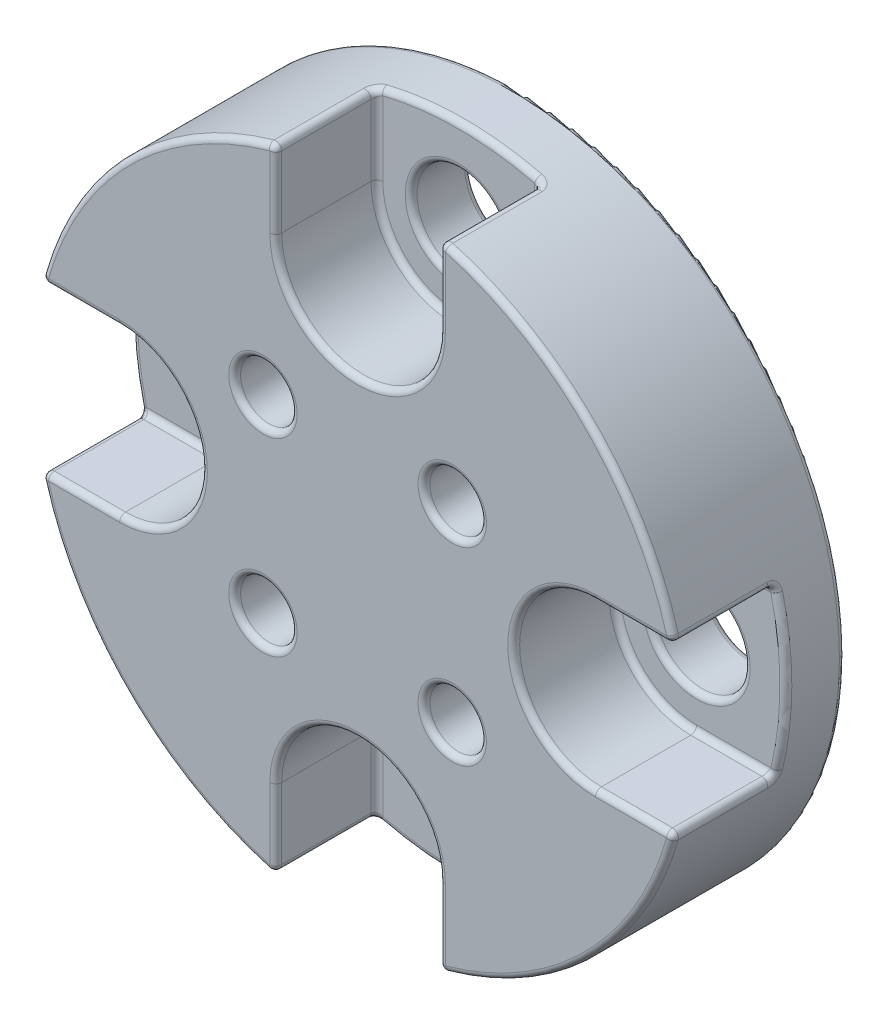
SolidWorks part; units mm, degrees
ref_plane "정면" through (0, 0, 0) normal (0, 0, 1) x (1, 0, 0)
ref_plane "윗면" through (0, 0, 0) normal (0, 1, 0) x (1, 0, 0)
ref_plane "우측면" through (0, 0, 0) normal (1, 0, 0) x (0, 0, -1)
sketch "스케치1" plane through (0, 0, 0) normal (0, 0, 1) x (1, 0, 0)
  circle A0 centre (0, 0) radius 15
  circle A1 centre (0, 0) radius 11.5
  dimension "D1" = 23
  dimension "D2" = 30
extrude "보스-돌출1" add sketch "스케치1" against normal blind 1.8 contours A0 A1 region at (-14.5757, 0, 0)
extrude "보스-돌출2" add sketch "스케치1<3>" along normal blind 2 contours A0 A1 | A1 region at (-14.5757, 0, 0)
sketch "스케치1<3>" plane through (0, 0, 0) normal (0, 0, 1) x (1, 0, 0) same geometry as "스케치1"
sketch "스케치2" plane through (0, 0, 2) normal (0, 0, 1) x (1, 0, 0)
  circle A0 centre (0, 8) radius 1.6
  circle A1 centre (8, 0) radius 1.6
  circle A2 centre (0, -8) radius 1.6
  circle A3 centre (-8, 0) radius 1.6
  point P12 (0, 0)
  dimension "D1" = 3.2
  dimension "D2" = 8
  dimension "D3" = 4
extrude "컷-돌출1" cut sketch "스케치2" against normal blind 2
sketch "스케치3" plane through (0, 0, 2) normal (0, 0, 1) x (1, 0, 0)
  line L0 (-8, 2.75) -> (-14.7458, 2.75)
  line L1 (-8, -2.75) -> (-14.7458, -2.75)
  line L2 (8, 2.75) -> (14.7458, 2.75)
  line L3 (8, -2.75) -> (14.7458, -2.75)
  line L4 (2.75, 8) -> (2.75, 14.7458)
  line L5 (-2.75, 8) -> (-2.75, 14.7458)
  line L6 (2.75, -8) -> (2.75, -14.7458)
  line L7 (-2.75, -8) -> (-2.75, -14.7458)
  arc A0 (-8, -2.75) -> (-8, 2.75) centre (-8, 0) ccw
  arc A1 (-2.75, 8) -> (2.75, 8) centre (0, 8) ccw
  arc A2 (8, 2.75) -> (8, -2.75) centre (8, 0) ccw
  arc A3 (2.75, -8) -> (-2.75, -8) centre (0, -8) ccw
  arc A4 (14.7458, 2.75) -> (2.75, 14.7458) centre (0, 0) ccw
  circle A5 centre (0, 0) radius 15
  arc A6 (-2.75, 14.7458) -> (-14.7458, 2.75) centre (0, 0) ccw
  arc A7 (-14.7458, -2.75) -> (-2.75, -14.7458) centre (0, 0) ccw
  arc A8 (2.75, -14.7458) -> (14.7458, -2.75) centre (0, 0) ccw
  dimension "D1" = 5.5
  dimension "D2" = 0
extrude "보스-돌출3" add sketch "스케치3" along normal blind 3.4 contours A1 L4 A4 L2 A2 L3 A8 L6 A3 L7 A7 L1 A0 L0 A6 L5
sketch "스케치4" plane through (0, 0, 5.4) normal (0, 0, 1) x (1, 0, 0)
  line L0 (0, 0) -> (16.9927, 0) construction
  line L1 (0, 0) -> (3.182, 3.182) construction
  circle A0 centre (3.182, 3.182) radius 0.95
  circle A1 centre (3.182, -3.182) radius 0.95
  circle A2 centre (-3.182, -3.182) radius 0.95
  circle A3 centre (-3.182, 3.182) radius 0.95
  point P14 (0, 0)
  dimension "D3" = 1.9
  dimension "D1" = 45
  dimension "D2" = 4.5
  dimension "D4" = 4
extrude "컷-돌출2" cut sketch "스케치4" against normal through all
sketch "스케치5" plane through (0, 0, 5.4) normal (0, 0, 1) x (1, 0, 0)
  circle A0 centre (0, 0) radius 11
  circle A1 centre (0, 0) radius 30.1031
  line M5 (-2.75, 8) -> (-2.75, 14.7458)
  arc M6 (-2.75, 14.7458) -> (-14.7458, 2.75) centre (0, 0) ccw
  line M7 (-14.7458, 2.75) -> (-8, 2.75)
  line M9 (-8, -2.75) -> (-14.7458, -2.75)
  arc M10 (-14.7458, -2.75) -> (-2.75, -14.7458) centre (0, 0) ccw
  line M11 (-2.75, -14.7458) -> (-2.75, -8)
  line M13 (2.75, -8) -> (2.75, -14.7458)
  arc M14 (2.75, -14.7458) -> (14.7458, -2.75) centre (0, 0) ccw
  line M15 (14.7458, -2.75) -> (8, -2.75)
  line M17 (8, 2.75) -> (14.7458, 2.75)
  arc M18 (14.7458, 2.75) -> (2.75, 14.7458) centre (0, 0) ccw
  line M19 (2.75, 14.7458) -> (2.75, 8)
  dimension "D1" = 22
extrude "컷-돌출3" cut sketch "스케치5" against normal through all contours A1 A0 M19 M18 M17 M15 M14 M13 M11 M10 M9 M7 M6 M5 | A0 M9 M10 M11 | A0 M5 M6 M7 | A0 M17 M18 M19 | A0 M13 M14 M15 region at (8.789, 8.789, 5.4) region at (8.789, -8.789, 5.4) region at (-8.789, 8.789, 5.4) region at (-8.789, -8.789, 5.4) region at (-29.2516, 0, 5.4)
fillet "필렛1" radius 0.2 57 edges at (2.75, -10.6507, 3.7) (-2.75, -10.6507, 3.7) (10.6507, 2.75, 3.7) (10.6507, -2.75, 3.7) (-2.75, 10.6507, 3.7) (2.75, 10.6507, 3.7) (-10.6507, -2.75, 3.7) (-10.6507, 2.75, 3.7) (11, 0, 0) (-2.232, 3.182, 0) (-2.232, -3.182, 0) (4.132, -3.182, 0) (4.132, 3.182, 0) (1.6, 8, 0) (9.6, 0, 0) (1.6, -8, 0) (-6.4, 0, 0) (0, -5.25, 2) (2.75, -9.3254, 2) (0, -11, 2) (-2.75, -9.3254, 2) (1.6, -8, 2) (5.25, 0, 2) (9.3254, 2.75, 2) (11, 0, 2) (9.3254, -2.75, 2) (9.6, 0, 2) (0, 5.25, 2) (-2.75, 9.3254, 2) (0, 11, 2) (2.75, 9.3254, 2) (1.6, 8, 2) (-5.25, 0, 2) (-9.3254, -2.75, 2) (-11, 0, 2) (-9.3254, 2.75, 2) (-6.4, 0, 2) (5.25, 0, 5.4) (9.3254, -2.75, 5.4) (7.7782, -7.7782, 5.4) (2.75, -9.3254, 5.4) (0, -5.25, 5.4) (-2.75, -9.3254, 5.4) (-7.7782, -7.7782, 5.4) (-9.3254, -2.75, 5.4) (-5.25, 0, 5.4) (-9.3254, 2.75, 5.4) (-7.7782, 7.7782, 5.4) (-2.75, 9.3254, 5.4) (0, 5.25, 5.4) (2.75, 9.3254, 5.4) (7.7782, 7.7782, 5.4) (9.3254, 2.75, 5.4) (4.132, 3.182, 5.4) (4.132, -3.182, 5.4) (-2.232, -3.182, 5.4) (-2.232, 3.182, 5.4)
